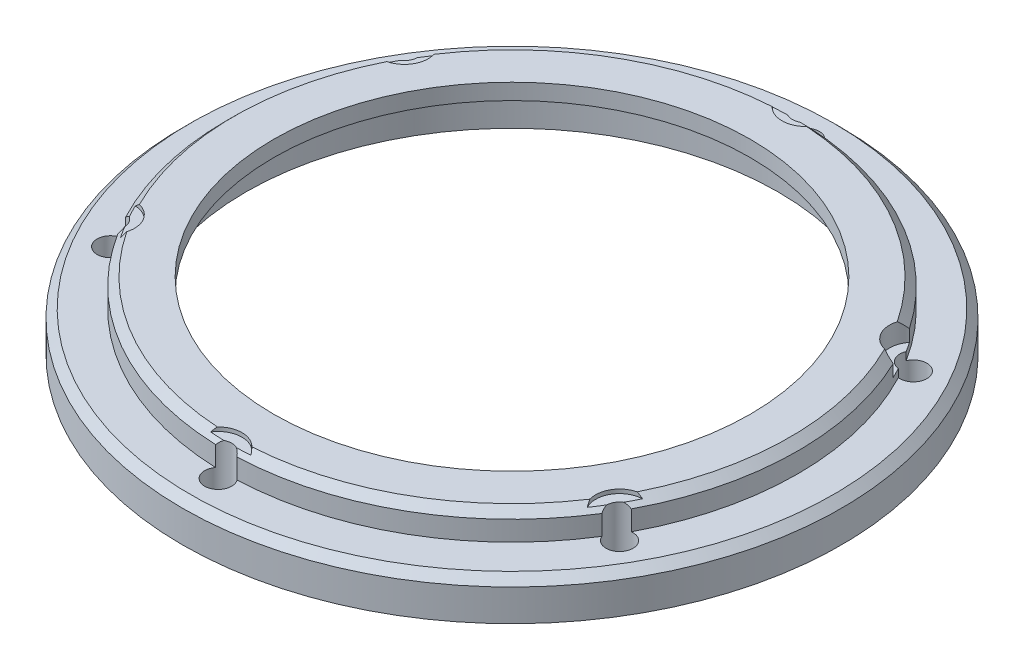
SolidWorks part; units mm, degrees
ref_plane "前视基准面" through (0, 0, 0) normal (0, 0, 1) x (1, 0, 0)
ref_plane "上视基准面" through (0, 0, 0) normal (0, 1, 0) x (1, 0, 0)
ref_plane "右视基准面" through (0, 0, 0) normal (1, 0, 0) x (0, 0, -1)
sketch "草图2" plane through (0, 0, 0) normal (1, 0, 0) x (0, 0, -1)
  line L9 (-30, 0) -> (-30, 2)
  line L10 (-30, 2) -> (-36, 2)
  line L11 (-30, 0) -> (-33.5, 0)
  line L12 (-33.5, 0) -> (-33.5, -5.5)
  line L13 (-33.5, -5.5) -> (-35, -5.5)
  line L14 (-35, -5.5) -> (-35, -6.5)
  line L15 (-35, -6.5) -> (-41.5, -6.5)
  line L16 (-36, 2) -> (-36, -1.5)
  line L17 (-36, -1.5) -> (-41.5, -1.5)
  line L18 (-41.5, -1.5) -> (-41.5, -6.5)
ref_axis "基准轴1" through (0, 0, 0) along (0, 1, 0)
revolve "旋转1" add sketch "草图2" angle 360 about axis through (0, 0, 0) along (0, 1, 0)
sketch "草图3" plane through (0, -1.5, 0) normal (0, 1, 0) x (1, 0, 0)
  circle A0 centre (0, 37) radius 1.7
  circle A1 centre (32.0429, 18.5) radius 1.7
  circle A2 centre (32.0429, -18.5) radius 1.7
  circle A3 centre (0, -37) radius 1.7
  circle A4 centre (-32.0429, -18.5) radius 1.7
  circle A5 centre (-32.0429, 18.5) radius 1.7
  point P16 (0, 0)
  dimension "D1" = 6
extrude "切除-拉伸1" cut sketch "草图3" against normal blind 10 and the other way up to next
sketch "草图4" plane through (0, -1.5, 0) normal (0, 1, 0) x (1, 0, 0)
  circle A0 centre (0, 37) radius 3
  circle A1 centre (32.0429, 18.5) radius 3
  circle A2 centre (32.0429, -18.5) radius 3
  circle A3 centre (0, -37) radius 3
  circle A4 centre (-32.0429, -18.5) radius 3
  circle A5 centre (-32.0429, 18.5) radius 3
  point P16 (0, 0)
  dimension "D1" = 6
extrude "切除-拉伸2" cut sketch "草图4" along normal blind 3 from offset 3
sketch "草图7" plane through (0, -1.5, 0) normal (0, 1, 0) x (1, 0, 0)
  circle A0 centre (32.0429, 18.5) radius 3
extrude "切除-拉伸3" cut sketch "草图7" along normal blind 10
sketch "草图8" plane through (0, -1.5, 0) normal (0, 1, 0) x (1, 0, 0)
  arc A1 (29.6894, 20.3603) -> (32.4772, 15.5316) centre (0, 0) cw
  arc A2 (29.6894, 20.3603) -> (32.4772, 15.5316) centre (32.0429, 18.5) ccw
  arc A3 (32.4772, -15.5316) -> (32.4772, 15.5316) centre (0, 0) ccw construction
  circle M2 centre (32.0429, 18.5) radius 1.7
  arc M4 (29.6894, 20.3603) -> (32.4772, 15.5316) centre (32.0429, 18.5) ccw
extrude "凸台-拉伸1" add sketch "草图8" along normal blind 1 contours A1 M4 M2
chamfer "倒角1" distance 1 angle 45 5 edges at (-18, 2, -31.1769) (18, 2, 31.1769) (-18, 2, 31.1769) (-36, 2, 0) (0, -1.5, -41.5)
